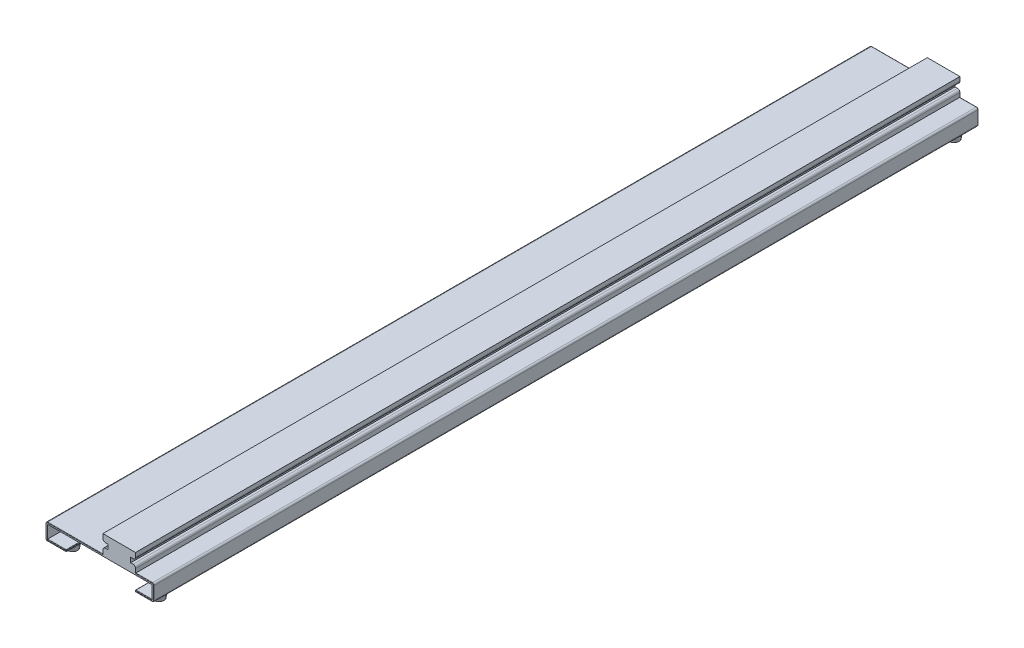
SolidWorks part; units mm, degrees
ref_plane "前视基准面" through (0, 0, 0) normal (0, 0, 1) x (1, 0, 0)
ref_plane "上视基准面" through (0, 0, 0) normal (0, 1, 0) x (1, 0, 0)
ref_plane "右视基准面" through (0, 0, 0) normal (1, 0, 0) x (0, 0, -1)
other "Configuration Table"
sketch "草图1" plane through (0, 0, 0) normal (0, 0, 1) x (1, 0, 0)
  line L0 (-27, 0) -> (-52, 0)
  line L1 (-52, 0) -> (-52, 20)
  line L2 (-52, 20) -> (18, 20)
  line L3 (18, 20) -> (18, 28)
  line L4 (18, 28) -> (24, 28)
  line L5 (24, 28) -> (24, 34)
  line L6 (24, 34) -> (18, 34)
  line L7 (18, 34) -> (18, 42)
  line L8 (18, 42) -> (58, 42)
  line L9 (58, 34) -> (58, 42)
  line L10 (52, 34) -> (58, 34)
  line L11 (52, 28) -> (52, 34)
  line L12 (58, 28) -> (52, 28)
  line L13 (58, 20) -> (58, 28)
  line L14 (60.4392, 20) -> (80.4392, 20)
  line L15 (80.4392, 20) -> (80.4392, 0)
  line L16 (80.4392, 0) -> (57.6503, 0)
  line L17 (18, 20) -> (60.4392, 20)
  line L18 (-27, 2) -> (-50, 2)
  line L19 (-50, 2) -> (-50, 18)
  line L20 (-50, 18) -> (18, 18)
  line L21 (18, 18) -> (60.4392, 18)
  line L22 (60.4392, 18) -> (78.4392, 18)
  line L23 (78.4392, 18) -> (78.4392, 2)
  line L24 (78.4392, 2) -> (57.6503, 2)
  line L25 (-27, 0) -> (-27, 2)
  line L26 (57.6503, 0) -> (57.6503, 2)
  line L27 (38, 20) -> (38, 46.341) construction
  point P12 (38, 42)
  dimension "D2" = 25
  dimension "D3" = 20
  dimension "D4" = 20
  dimension "D5" = 27
  dimension "D6" = 70
  dimension "D7" = 8
  dimension "D8" = 6
  dimension "D10" = 6
  dimension "D11" = 20
  dimension "D1" = 2
extrude "凸台-拉伸1" add sketch "草图1" against normal blind 1010 contours L27 L17 L13 L12 L11 L10 L9 L8 | L17 L27 L8 L7 L6 L5 L4 L3 | L17 L14 L15 L16 L26 L24 L23 L22 L21 L20 L19 L18 L25 L0 L1 L2 region at (28.6238, 31, 0) region at (47.3762, 31, 0)
fillet "圆角1" radius 2 4 edges at (80.4392, 0, -505) (80.4392, 20, -505) (-52, 0, -505) (-52, 20, -505)
fillet "圆角2" radius 0.5 4 edges at (57.6503, 0, -505) (57.6503, 2, -505) (-27, 0, -505) (-27, 2, -505)
fillet "圆角3" radius 0.5 36 edges at (-16, 20, -1010) (-51.4142, 19.4142, -1010) (-52, 10, -1010) (-51.4142, 0.5858, -1010) (-38.75, 0, -1010) (-27.1464, 0.1464, -1010) (-38.75, 2, -1010) (-27.1464, 1.8536, -1010) (-16, 20, 0) (-51.4142, 19.4142, 0) (-52, 10, 0) (-51.4142, 0.5858, 0) (-38.75, 0, 0) (-27.1464, 0.1464, 0) (-38.75, 2, 0) (-27.1464, 1.8536, 0) (68.2196, 20, -1010) (79.8534, 19.4142, -1010) (80.4392, 10, -1010) (79.8534, 0.5858, -1010) (68.2947, 0, -1010) (57.7967, 0.1464, -1010) (68.2947, 2, -1010) (57.7967, 1.8536, -1010) (68.2196, 20, 0) (79.8534, 19.4142, 0) (80.4392, 10, 0) (79.8534, 0.5858, 0) (68.2947, 0, 0) (57.7967, 0.1464, 0) (68.2947, 2, 0) (57.7967, 1.8536, 0) (-27, 1, -1010) (-27, 1, 0) (57.6503, 1, -1010) (57.6503, 1, 0)
fillet "圆角4" radius 3 4 edges at (18, 28, -505) (18, 34, -505) (58, 28, -505) (58, 34, -505)
sketch "草图2" plane through (0, 0, 0) normal (0, -1, 0) x (1, 0, 0)
  line L1 (80.4392, -0.5) -> (80.4392, -1009.5) construction
  line L2 (78.4392, -0.5) -> (58.1503, -0.5) construction
  circle A0 centre (68.4392, -18.5) radius 8
  circle A1 centre (-37.5608, -18.5) radius 8
  circle A2 centre (-37.5608, -992.5) radius 8
  circle A3 centre (68.4392, -992.5) radius 8
  dimension "D3" = 16
  dimension "D1" = 12
  dimension "D2" = 18
  dimension "D4" = 2
  dimension "D5" = 2
ref_plane "基准面1" through (0, -10, 0) normal (0, -1, 0) x (-1, 0, 0)
sketch "草图3" plane through (0, -10, 0) normal (0, -1, 0) x (-1, 0, 0)
  circle A0 centre (-68.4392, 18.5) radius 6
  circle A1 centre (37.5608, 18.5) radius 6
  circle A2 centre (-68.4392, 992.5) radius 6
  circle A3 centre (37.5608, 992.5) radius 6
  point P0 (37.5608, 18.5)
  point P2 (-68.4392, 18.5)
  point P4 (37.5608, 992.5)
  point P6 (-68.4392, 992.5)
  dimension "D1" = 12
  dimension "D2" = 12
  dimension "D3" = 12
  dimension "D4" = 12
loft "放样1" add section "草图3" section "草图2" connector at (70.8462, -10, -13.004) connector at (68.1929, 0, -10.5038)
pattern_linear "阵列(线性)1" count 2 spacing 106 along (-1, 0, 0) count 2 spacing 974 along (0, 0, -1) of "放样1"
